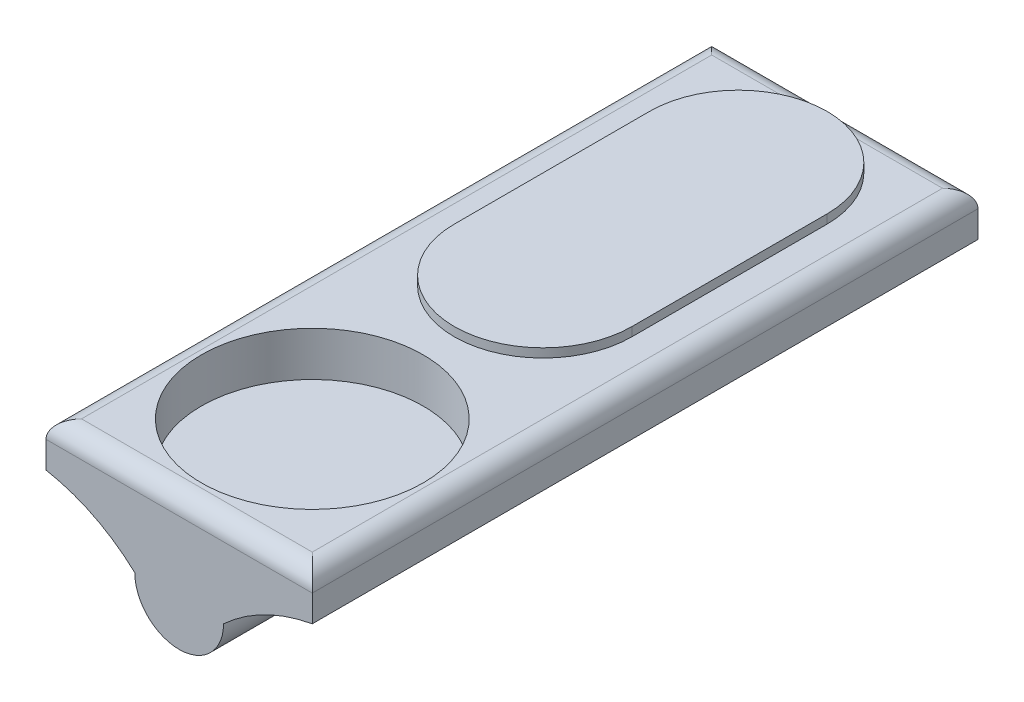
SolidWorks part; units mm, degrees
ref_plane "Front Plane" through (0, 0, 0) normal (0, 0, 1) x (1, 0, 0)
ref_plane "Top Plane" through (0, 0, 0) normal (0, 1, 0) x (1, 0, 0)
ref_plane "Right Plane" through (0, 0, 0) normal (1, 0, 0) x (0, 0, -1)
sketch "Sketch1" plane through (0, 0, 0) normal (0, 0, 1) x (1, 0, 0)
  line L1 (-15, 10) -> (15, 10)
  line L2 (15, 10) -> (15, 5)
  line L3 (-15, 10) -> (-15, 5)
  arc A0 (-5, 0) -> (5, 0) centre (0, 0) ccw
  arc A1 (-15, 5) -> (-5, 0) centre (-18.5878, -14.6756) cw
  arc A2 (5, 0) -> (15, 5) centre (18.5878, -14.6756) cw
  point P7 (0, 10)
  dimension "D4" = 10
  dimension "D5" = 20
  dimension "D6" = 20
  dimension "D2" = 5
  dimension "D3" = 5
  dimension "D7" = 30
extrude "Boss-Extrude1" add sketch "Sketch1" against normal blind 75
sketch "Sketch3" plane through (0, 0, -75) normal (0, 0, -1) x (-1, 0, 0)
  circle A0 centre (0, 0) radius 4
extrude "Cut-Extrude1" cut sketch "Sketch3" against normal blind 65
sketch "Sketch4" plane through (0, 10, 0) normal (0, 1, 0) x (1, 0, 0)
  line L0 (-15, 75) -> (-15, 0) construction
  line L2 (-10, 63) -> (-10, 41)
  line L4 (10, 63) -> (10, 41)
  line L5 (-8.2693, 68.623) -> (8.2693, 35.377) construction
  line L6 (-8.2693, 35.377) -> (5.7001, 71.2163) construction
  line L7 (15, 75) -> (15, 0) construction
  line L8 (15, 75) -> (-15, 75) construction
  arc A0 (10, 63) -> (-10, 63) centre (0, 63) ccw
  arc A1 (-10, 41) -> (10, 41) centre (0, 41) ccw
  point P0 (-1.0036, 54.0175)
  dimension "D1" = 5
  dimension "D3" = 12
  dimension "D2" = 5
  dimension "D4" = 22
extrude "Boss-Extrude2" add sketch "Sketch4" along normal blind 1
sketch "Sketch5" plane through (0, 10, 0) normal (0, 1, 0) x (1, 0, 0)
  line L0 (15, 0) -> (-15, 0) construction
  circle A0 centre (0, 15) radius 12.5
  dimension "D1" = 15
  dimension "D2" = 25
extrude "Cut-Extrude2" cut sketch "Sketch5" against normal blind 5
fillet "Fillet1" radius 2 4 edges at (0, 10, 0) (15, 10, -37.5) (0, 10, -75) (-15, 10, -37.5)
